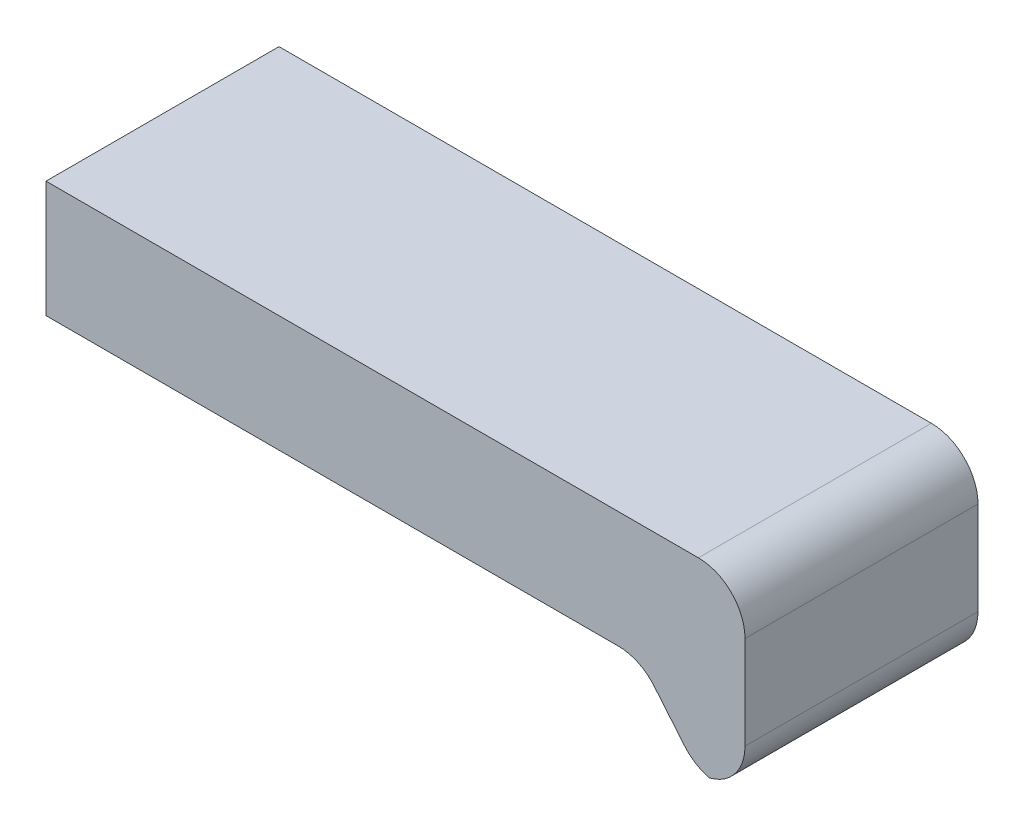
SolidWorks part; units mm, degrees
ref_plane "Front Plane" through (0, 0, 0) normal (0, 0, 1) x (1, 0, 0)
ref_plane "Top Plane" through (0, 0, 0) normal (0, 1, 0) x (1, 0, 0)
ref_plane "Right Plane" through (0, 0, 0) normal (1, 0, 0) x (0, 0, -1)
sketch "Sketch1" plane through (0, 0, 0) normal (0, 0, 1) x (1, 0, 0)
  line L0 (0, 2.5) -> (15, 2.5)
  line L2 (15, 2.5) -> (15, -1.5)
  line L3 (15, -1.5) -> (14, -1.5)
  line L4 (14, -1.5) -> (12.75, 0)
  line L5 (12.75, 0) -> (0, 0)
  line L6 (0, 0) -> (0, 2.5)
  point P2 (0, 0)
  dimension "D2" = 2.5
  dimension "D3" = 4
  dimension "D4" = 12.75
  dimension "D8" = 1.25
  dimension "D10" = 15
extrude "Boss-Extrude1" add sketch "Sketch1" along normal blind 5 contours L5 L6 L0 L2 L3 L4
fillet "Fillet1" radius 1 4 edges at (15, 2.5, 2.5) (15, -1.5, 2.5) (12.75, 0, 2.5) (14, -1.5, 2.5)
